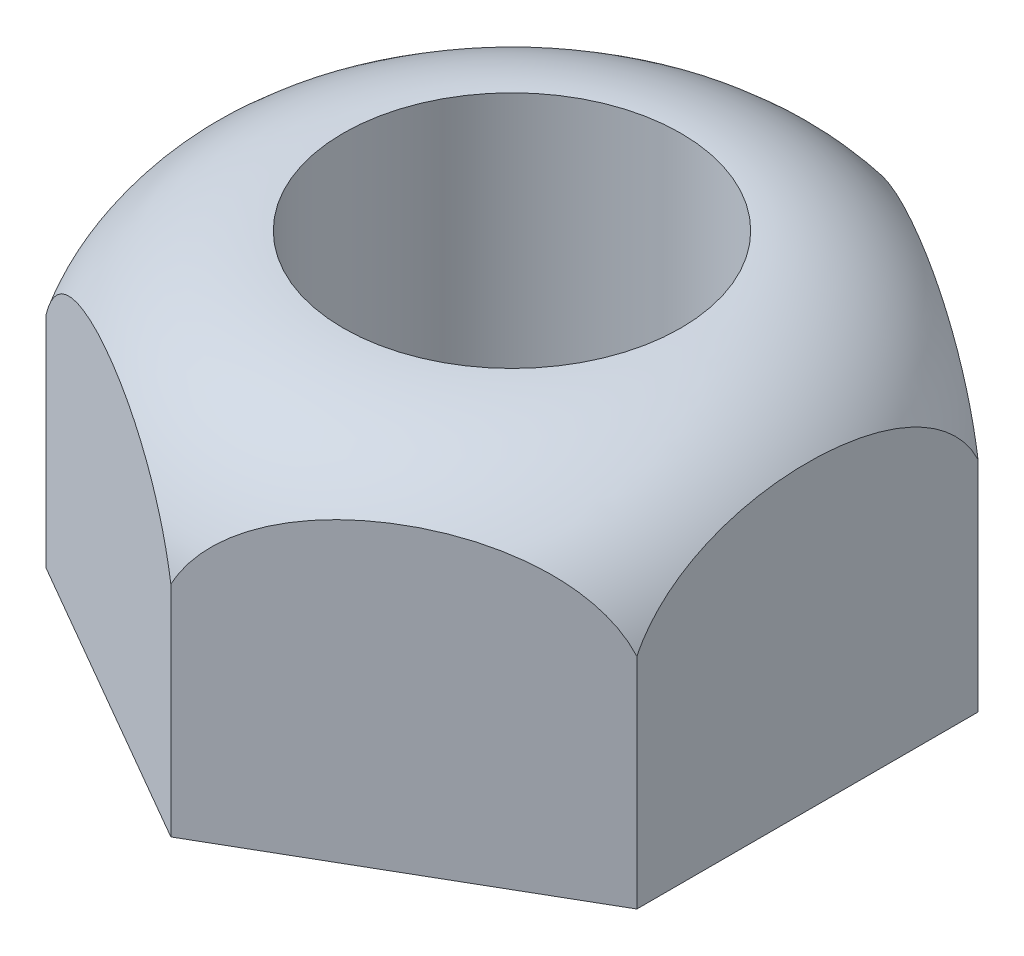
SolidWorks part; units mm, degrees
ref_plane "Front Plane" through (0, 0, 0) normal (0, 0, 1) x (1, 0, 0)
ref_plane "Top Plane" through (0, 0, 0) normal (0, 1, 0) x (1, 0, 0)
ref_plane "Right Plane" through (0, 0, 0) normal (1, 0, 0) x (0, 0, -1)
sketch "Sketch1" plane through (0, 0, 0) normal (0, 1, 0) x (1, 0, 0)
  line L0 (0, 2) -> (0, 1.3) construction
  line L1 (0, 4.0415) -> (-3.5, 2.0207) construction
  line L2 (-3.5, 2.0207) -> (-3.5, -2.0207) construction
  line L3 (-3.5, -2.0207) -> (0, -4.0415) construction
  line L4 (0, -4.0415) -> (3.5, -2.0207) construction
  line L5 (3.5, -2.0207) -> (3.5, 2.0207) construction
  line L6 (3.5, 2.0207) -> (0, 4.0415) construction
  circle A0 centre (0, 0) radius 3.5 construction
  circle A1 centre (0, 0) radius 2 construction
  point P12 (0, -2)
  dimension "Thread Size" = 4
  dimension "Width" = 7
  dimension "Thread Pitch" = 0.7
sketch "Sketch2" plane through (0, 0, 0) normal (0, 0, 1) x (1, 0, 0)
  line L0 (0, -2.1) -> (0, 2.1) construction
  point P4 (0, 0)
  dimension "Height" = 4.2
sketch "Sketch3" plane through (0, 0, 0) normal (0, 1, 0) x (1, 0, 0)
  line L0 (3.5, 2.0207) -> (0, 4.0415) construction
  line L1 (3.5, -2.0207) -> (3.5, 2.0207) construction
  line L2 (0, -4.0415) -> (3.5, -2.0207) construction
  line L3 (-3.5, -2.0207) -> (0, -4.0415) construction
  line L4 (-3.5, 2.0207) -> (-3.5, -2.0207) construction
  line L5 (0, 4.0415) -> (-3.5, 2.0207) construction
  line L6 (3.5, 2.0207) -> (0, 4.0415)
  line L7 (3.5, -2.0207) -> (3.5, 2.0207)
  line L8 (0, -4.0415) -> (3.5, -2.0207)
  line L9 (-3.5, -2.0207) -> (0, -4.0415)
  line L10 (-3.5, 2.0207) -> (-3.5, -2.0207)
  line L11 (0, 4.0415) -> (-3.5, 2.0207)
  circle A0 centre (0, 0) radius 2 construction
  circle A1 centre (0, 0) radius 2
extrude "Boss-Extrude1" add sketch "Sketch3" along normal mid plane 4.2
ref_plane "Plane1" through (0, 2.1, 0) normal (0, 1, 0) x (1, 0, 0)
sketch "Sketch5" plane through (0, 0, 0) normal (1, 0, 0) x (0, 0, -1)
  line L0 (4.0415, 2.1) -> (4.0415, -2.1) construction
  line L1 (2.0207, 2.1) -> (4.0415, 2.1) construction
  line L3 (2, 2.1) -> (4.0415, 2.1)
  line L4 (4.0415, 2.1) -> (4.0415, 0.4924)
  line L5 (0, 0) -> (0, 1.85) construction
  line L6 (0, -2.1) -> (0, 2.1) construction
  arc A0 (2, 2.1) -> (4.0415, 0.4924) centre (2, 0) cw
  dimension "D1" = 2.1
revolve "Cut-Revolve1" cut sketch "Sketch5" angle 360 about L5
sketch "Ref" plane through (0, 0, 0) normal (0, 0, 1) x (1, 0, 0)
  line L0 (-3.5, -2.1) -> (-3.5, 2.1) construction
  dimension "D1" = 4.2
sketch "Sketch7" [suppressed] plane through (0, 2.1, 0) normal (0, 1, 0) x (1, 0, 0)
  circle A0 centre (0, 0) radius 2 construction
  circle A1 centre (0, 0) radius 2
curve "Helix/Spiral1" [suppressed] pitch 0.7 height 4.9 turns 7
sketch "Sketch8" [suppressed] plane through (0, 0, 0) normal (0, 0, 1) x (1, 0, 0)
  line L0 (-2, 2.7125) -> (-2, 2.1)
  line L1 (-2, 2.1) -> (-1.5453, 2.3625)
  line L2 (-1.5453, 2.45) -> (-2, 2.7125)
  line L3 (-1.5453, 2.45) -> (-1.5453, 2.3625)
  line L4 (-1.5453, 2.4062) -> (-2, 2.4062) construction
  line L5 (-1.7727, 2.2312) -> (-1.7727, 2.5812) construction
  point P11 (-1.7727, 2.4062)
  dimension "D1" = 60
  dimension "D2" = 0.0875
  dimension "D3" = 0.35
sweep "Sweep1" [suppressed] add profiles "Sketch8" path "Helix/Spiral1"
sketch "Sketch9" [suppressed] plane through (0, 2.1, 0) normal (0, 1, 0) x (1, 0, 0)
  circle A1 centre (0, 0) radius 2
  circle A2 centre (0, 0) radius 2
  dimension "D1" = 0
extrude "Cut-Extrude2" [suppressed] cut sketch "Sketch9" along normal through all
mirror "Mirror1" [suppressed] about plane through (0, 0, 0) normal (0, 1, 0)
sketch "Sketch10" [suppressed] plane through (0, 2.1, 0) normal (0, 1, 0) x (1, 0, 0)
  circle A0 centre (0, 0) radius 2.07
  circle A2 centre (0, 0) radius 2 construction
  dimension "D2" = 4
  dimension "D1" = 0.07
extrude "Cut-Extrude3" [suppressed] cut sketch "Sketch10" against normal through all draft 45
equation "\"D1@Boss-Extrude1\"=\"Height@Sketch2\""
equation "\"D1@Sketch5\"=(\"Height@Sketch2\"*.5)"
equation "\"D4@Helix/Spiral1\"=\"Thread Pitch@Sketch1\""
equation "\"D3@Helix/Spiral1\"=\"Height@Sketch2\"+\"Thread Pitch@Sketch1\""
equation "\"D2@Sketch8\"=\"Thread Pitch@Sketch1\"*.125"
equation "\"D3@Sketch8\"=\"Thread Pitch@Sketch1\"*.5"
equation "\"D3@Cut-Extrude3\"=\"Thread Pitch@Sketch1\"*.75"
equation "\"D1@Sketch10\"=\"Thread Pitch@Sketch1\"*.1"
equation "\"D2@Sketch10\"=\"Thread Size@Sketch1\""
equation "\"D1@Ref\"=\"Height@Sketch2\""
